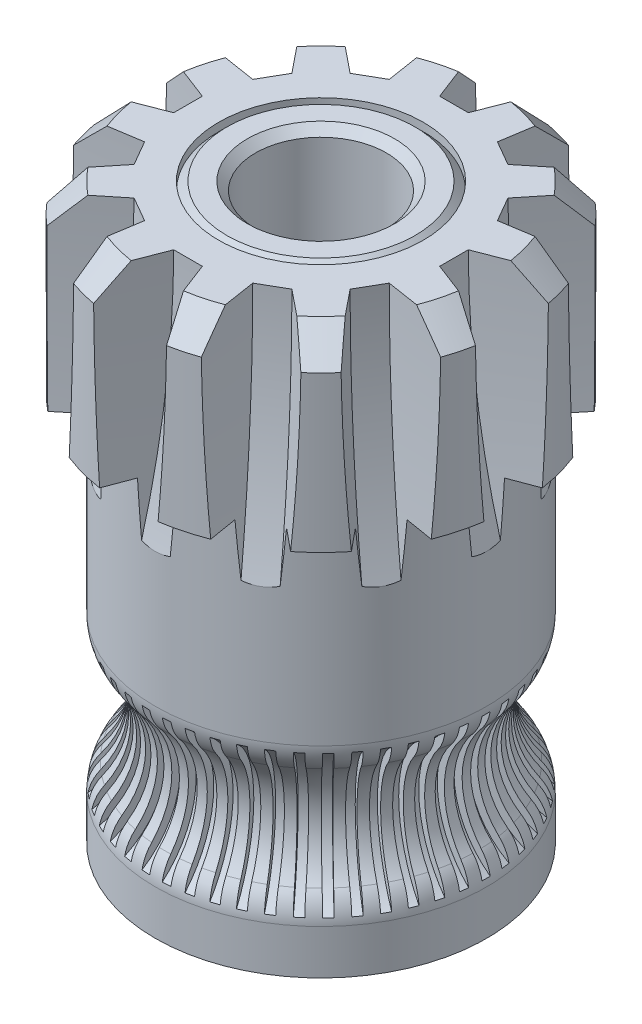
SolidWorks part; units mm, degrees
ref_plane "Front Plane" through (0, 0, 0) normal (0, 0, 1) x (1, 0, 0)
ref_plane "Top Plane" through (0, 0, 0) normal (0, 1, 0) x (1, 0, 0)
ref_plane "Right Plane" through (0, 0, 0) normal (1, 0, 0) x (0, 0, -1)
sketch "Sketch1" plane through (0, 0, 0) normal (0, 0, 1) x (1, 0, 0)
  line L0 (0, 0) -> (0, 14) construction
  line L2 (4.05, 0) -> (4.05, 1.0895)
  line L3 (4.05, 4.5) -> (4.05, 1.5) construction
  line L4 (2.5, 14) -> (4.05, 14)
  line L5 (4.05, 14) -> (4.05, 9.5) construction
  line L6 (4.05, 9.5) -> (4.75, 9.5)
  line L7 (4.05, 14) -> (4.75, 13.3)
  line L8 (4.75, 13.3) -> (4.75, 9.5)
  line L9 (4.05, 9.5) -> (4.05, 4.9105)
  line L10 (4.05, 3) -> (3.35, 3) construction
  line L11 (2.5, 0) -> (4.05, 0)
  line L12 (2.5, 0) -> (2.5, 14)
  arc A0 (3.8133, 4.2644) -> (3.8133, 1.7356) centre (5.3071, 3) ccw
  arc A1 (4.05, 1.0895) -> (3.8133, 1.7356) centre (3.05, 1.0895) ccw
  arc A2 (3.8133, 4.2644) -> (4.05, 4.9105) centre (3.05, 4.9105) ccw
  dimension "D1" = 1
revolve "Revolve1" add sketch "Sketch1" angle 360 about L0
sketch "Sketch4" plane through (0, 14, 0) normal (0, 1, 0) x (1, 0, 0)
  line L0 (4.75, 0) -> (3.25, 0) construction
  line L1 (3.25, -0.35) -> (3.25, 0.35)
  line L2 (3.25, 0.35) -> (4.75, 0.9276)
  line L3 (4.75, 0.9276) -> (4.75, -0.9276)
  line L4 (3.25, -0.35) -> (4.75, -0.9276)
  circle A0 centre (0, 0) radius 4.75 construction
sketch "Sketch5" plane through (0, 0, 0) normal (0, 0, 1) x (1, 0, 0)
  line L0 (4.75, 14) -> (24.75, 14) construction
  line L1 (3.25, 14) -> (4.75, 14) construction
  line L2 (4.75, 14) -> (3.25, 14) construction
  circle A0 centre (24.75, 14) radius 20
sweep "Cut-Sweep1" cut profiles "Sketch4" path "Sketch5"
pattern_circular "CirPattern1" count 12 over 360 about axis through (0, 0, 0) along (0, -1, 0) of "Cut-Sweep1"
sketch "Sketch6" plane through (0, 0, 0) normal (0, 0, 1) x (1, 0, 0)
  line L0 (5.6316, 5.1326) -> (5.6313, 0.8673)
  arc A2 (3.6606, 4.3936) -> (3.6606, 1.6064) centre (5.3071, 3) ccw
  arc A3 (5.6316, 5.1326) -> (5.6313, 0.8673) centre (5.3071, 3) ccw
  dimension "D1" = 0.2
extrude "Cut-Extrude1" cut sketch "Sketch6" against normal blind 0.1 and the other way blind 0.1
pattern_circular "CirPattern2" count 50 over 360 about axis through (0, 0, 0) along (0, -1, 0) of "Cut-Extrude1"
sketch "Sketch7" plane through (0, 0, 0) normal (0, 1, 0) x (1, 0, 0)
  circle A0 centre (0, 0) radius 2.5
  circle A1 centre (0, 0) radius 1.6
extrude "Boss-Extrude1" add sketch "Sketch7" along normal up to surface (14 mm away) separate body up to face at (0, 14, -2.5)
chamfer "Chamfer1" distance 0.2 angle 45 4 edges at (0, 0, 1.6) (0, 0, 2.5) (0, 14, 2.5) (0, 14, 1.6)
